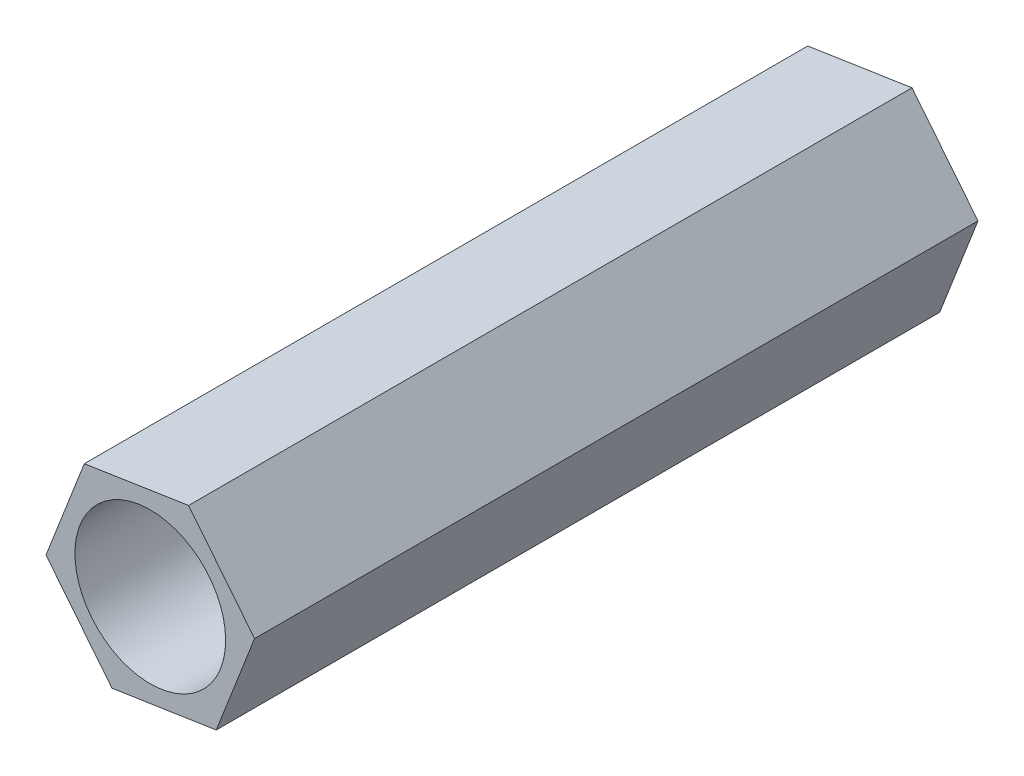
SolidWorks part; units mm, degrees
ref_plane "Front Plane" through (0, 0, 0) normal (0, 0, 1) x (1, 0, 0)
ref_plane "Top Plane" through (0, 0, 0) normal (0, 1, 0) x (1, 0, 0)
ref_plane "Right Plane" through (0, 0, 0) normal (1, 0, 0) x (0, 0, -1)
sketch "Sketch1" plane through (0, 0, 0) normal (0, 0, 1) x (1, 0, 0)
  circle A0 centre (0, 0) radius 1.25
  circle A1 centre (0, 0) radius 1.75
  dimension "D1" = 2.5
  dimension "D2" = 3.5
extrude "Boss-Extrude1" add sketch "Sketch1" along normal blind 12
sketch "Sketch2" plane through (0, 0, 12) normal (0, 0, 1) x (1, 0, 0)
  line L1 (1.0943, -1.3656) -> (1.7298, 0.2649)
  line L2 (1.7298, 0.2649) -> (0.6355, 1.6305)
  line L3 (0.6355, 1.6305) -> (-1.0943, 1.3656)
  line L4 (-1.0943, 1.3656) -> (-1.7298, -0.2649)
  line L5 (-1.7298, -0.2649) -> (-0.6355, -1.6305)
  line L6 (-0.6355, -1.6305) -> (1.0943, -1.3656)
  circle A0 centre (0, 0) radius 1.5155 construction
  circle M7 centre (0, 0) radius 1.75
  dimension "D1" = 1.75
extrude "Cut-Extrude2" cut sketch "Sketch2" against normal blind 12 contours L4 M7 | L3 M7 | L2 M7 | L1 M7 | L6 M7 | L5 M7 region at (0.2437, -1.5913, 12) region at (1.5, -0.5846, 12) region at (1.2563, 1.0067, 12) region at (-1.2563, -1.0067, 12) region at (-0.2437, 1.5913, 12) region at (-1.5, 0.5846, 12)
